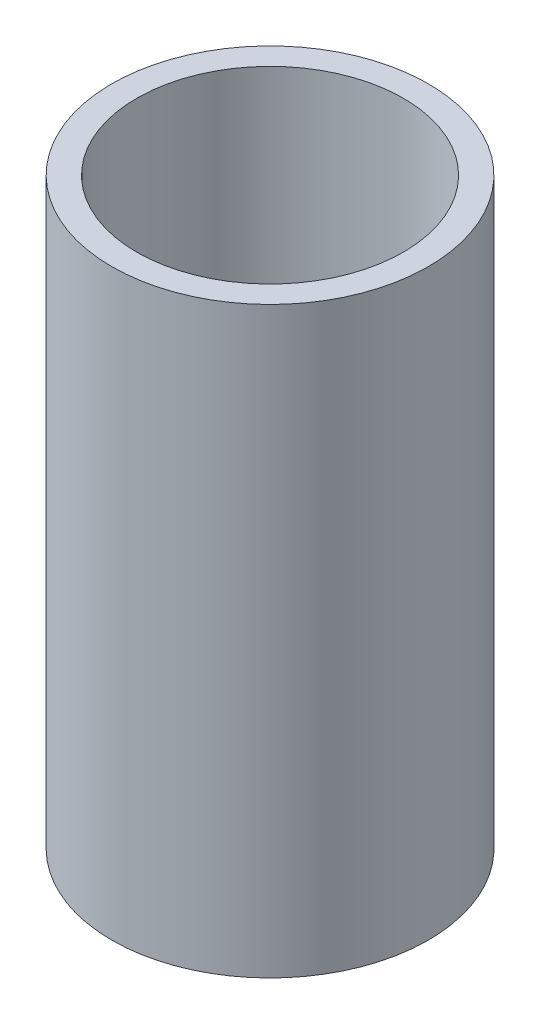
SolidWorks part; units mm, degrees
ref_plane "Front Plane" through (0, 0, 0) normal (0, 0, 1) x (1, 0, 0)
ref_plane "Top Plane" through (0, 0, 0) normal (0, 1, 0) x (1, 0, 0)
ref_plane "Right Plane" through (0, 0, 0) normal (1, 0, 0) x (0, 0, -1)
sketch "Sketch1" plane through (0, 0, 0) normal (0, 1, 0) x (1, 0, 0)
  circle A0 centre (0, 0) radius 20.32
  circle A1 centre (0, 0) radius 0.5
  circle A2 centre (0, 0) radius 24.13
  dimension "D1" = 48.26
  dimension "D2" = 40.64
extrude "Boss-Extrude1" add sketch "Sketch1" along normal blind 88.9 contours A2 A0 region at (-23.4475, 0, 0)
